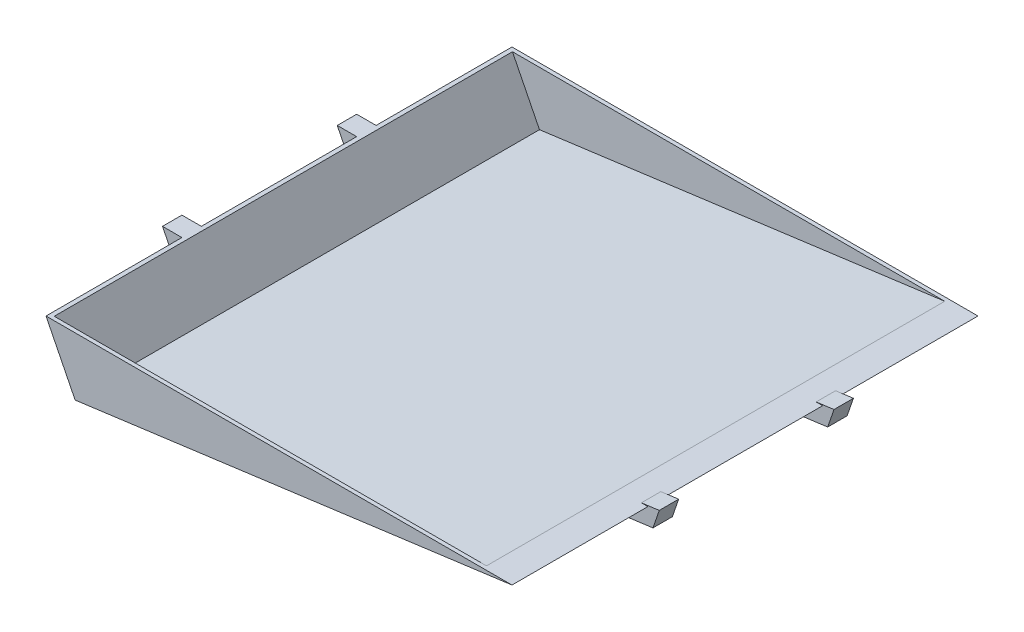
SolidWorks part; units mm, degrees
ref_plane "Front Plane" through (0, 0, 0) normal (0, 0, 1) x (1, 0, 0)
ref_plane "Top Plane" through (0, 0, 0) normal (0, 1, 0) x (1, 0, 0)
ref_plane "Right Plane" through (0, 0, 0) normal (1, 0, 0) x (0, 0, -1)
sketch3d "3DSketch1"
  line L2 (574.7508, 1402.4171, 1756.2546) -> (612.8508, 1326.2171, 1756.2546)
  line L3 (612.8508, 1326.2171, 1756.2546) -> (1184.3508, 1402.4171, 1756.2546)
  line L4 (1184.3508, 1402.4171, 1756.2546) -> (574.7508, 1402.4171, 1756.2546)
extrude "Boss-Extrude1" add sketch "3DSketch1" along a picked direction on the side of the normal blind 609.6 contours L2 L3 L4
shell "Shell1" thickness 5.08 removed face at (1031.9508, 1402.4171, 1603.8546)
sketch "Sketch1" plane through (0, 1402.4171, 0) normal (0, 1, 0) x (1, 0, 0)
  line L0 (562.0508, -1756.2546) -> (562.0508, -1146.6546) construction
  line L1 (1184.3508, -1756.2546) -> (574.7508, -1756.2546) construction
  line L2 (1184.3508, -1146.6546) -> (574.7508, -1146.6546) construction
  line L3 (574.7508, -1756.2546) -> (574.7508, -1146.6546) construction
  line L5 (574.7508, -1553.0546) -> (549.3508, -1553.0546)
  line L6 (574.7508, -1553.0546) -> (574.7508, -1578.4546)
  line L7 (574.7508, -1578.4546) -> (549.3508, -1578.4546)
  line L8 (549.3508, -1553.0546) -> (549.3508, -1578.4546)
  line L9 (574.7508, -1553.0546) -> (549.3508, -1578.4546) construction
  line L10 (574.7508, -1578.4546) -> (549.3508, -1553.0546) construction
  point P8 (562.0508, -1565.7546)
  dimension "D1" = 0
  dimension "D2" = 0
  dimension "D3" = 12.7
  dimension "D4" = 0
  dimension "D5" = 190.5
  dimension "D7" = 25.4
ref_plane "Plane1" through (0, 0, 1565.7546) normal (0, 0, 1) x (1, 0, 0)
sketch "Sketch3" plane through (0, 0, 1565.7546) normal (0, 0, 1) x (1, 0, 0)
  line L0 (562.0508, 1402.4171) -> (605.7838, 1314.9511)
  line L1 (574.7508, 1402.4171) -> (612.8508, 1326.2171) construction
  line L3 (605.7838, 1314.9511) -> (1195.0638, 1393.5217)
  line L4 (612.8508, 1326.2171) -> (1184.3508, 1402.4171) construction
  dimension "D1" = 97.79
  dimension "D2" = 0
  dimension "D3" = 589.28
  dimension "D4" = 0
sweep "Sweep1" add profiles "Sketch1" path "Sketch3"
ref_plane "Plane2" through (0, 0, 1451.4546) normal (0, 0, 1) x (1, 0, 0)
mirror "Mirror1" about plane through (0, 0, 1451.4546) normal (0, 0, 1) of "Sweep1"
sketch "Sketch4" plane through (0, 0, 1553.0546) normal (0, 0, -1) x (-1, 0, 0)
  line L0 (-599.2493, 1302.6201) -> (-624.6493, 1306.0067)
  line L1 (-599.2493, 1302.6201) -> (-1190.9353, 1381.5115) construction
  line L2 (-599.2493, 1302.6201) -> (-587.8901, 1325.3385)
  line L3 (-549.3508, 1402.4171) -> (-599.2493, 1302.6201) construction
  line L4 (-624.6493, 1306.0067) -> (-612.8508, 1326.2171)
  line L5 (-612.8508, 1326.2171) -> (-587.8901, 1325.3385)
  dimension "D1" = 25.4
  dimension "D2" = 25.4
extrude "Boss-Extrude5" add sketch "Sketch4" along normal blind 203.2 separate body
